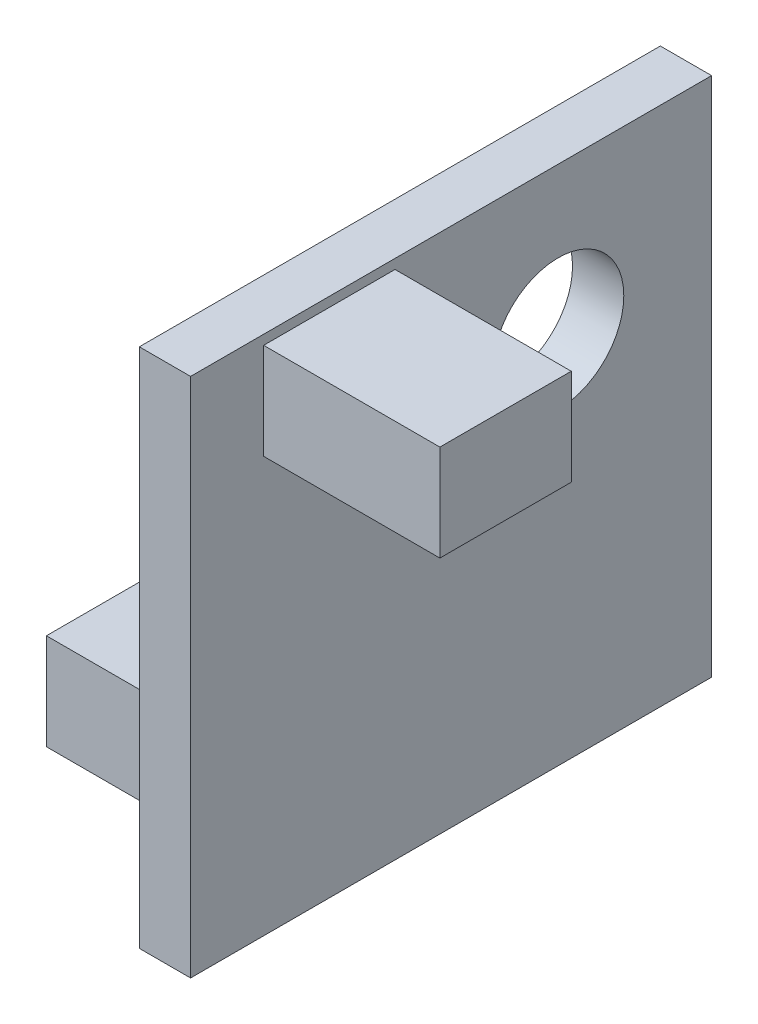
SolidWorks part; units mm, degrees
ref_plane "Front Plane" through (0, 0, 0) normal (0, 0, 1) x (1, 0, 0)
ref_plane "Top Plane" through (0, 0, 0) normal (0, 1, 0) x (1, 0, 0)
ref_plane "Right Plane" through (0, 0, 0) normal (1, 0, 0) x (0, 0, -1)
sketch "Sketch1" plane through (0, 0, 0) normal (1, 0, 0) x (0, 0, -1)
  line L1 (0, 0) -> (16.26, 0)
  line L2 (0, 0) -> (0, -16.26)
  line L3 (0, -16.26) -> (16.26, -16.26)
  line L4 (16.26, 0) -> (16.26, -16.26)
  line L5 (2.28, -0.3) -> (6.38, -0.3)
  line L6 (2.28, -0.3) -> (2.28, -3.3)
  line L7 (2.28, -3.3) -> (6.38, -3.3)
  line L8 (6.38, -0.3) -> (6.38, -3.3)
  dimension "D1" = 16.26
  dimension "D2" = 16.26
  dimension "D3" = 0.3
  dimension "D4" = 9.88
  dimension "D5" = 4.1
  dimension "D6" = 3
extrude "Boss-Extrude1" add sketch "Sketch1" along normal blind 1.6 contours L8 L5 L6 L7 | L4 L1 L2 L3 L5 L8 L7 L6 region at (0, -8.4389, -8.3154) region at (0, -1.8, -4.33)
extrude "Boss-Extrude2" add sketch "Sketch1<3>" along normal blind 7.1 contours L8 L5 L6 L7 region at (0, -1.8, -4.33)
sketch "Sketch1<3>" plane through (0, 0, 0) normal (1, 0, 0) x (0, 0, -1) same geometry as "Sketch1"
sketch "Sketch2" plane through (1.6, 0, 0) normal (1, 0, 0) x (0, 0, -1)
  line L0 (0, -16.26) -> (16.26, -16.26) construction
  line L1 (0, 0) -> (0, -16.26) construction
  circle A0 centre (11.47, -4.58) radius 2.05
  point P4 (0, 0)
  dimension "D1" = 4.1
  dimension "D2" = 11.68
  dimension "D3" = 11.47
extrude "Cut-Extrude1" cut sketch "Sketch2" against normal through all
sketch "Sketch3" plane through (1.6, 0, 0) normal (1, 0, 0) x (0, 0, -1)
  line L0 (0, -16.26) -> (16.26, -16.26) construction
  line L1 (2, -11.26) -> (9.5, -11.26)
  line L2 (2, -11.26) -> (2, -14.26)
  line L3 (2, -14.26) -> (9.5, -14.26)
  line L4 (9.5, -11.26) -> (9.5, -14.26)
  line L5 (0, 0) -> (0, -16.26) construction
  dimension "D1" = 3
  dimension "D2" = 7.5
  dimension "D3" = 2
  dimension "D4" = 2
extrude "Boss-Extrude3" add sketch "Sketch3" against normal blind 6.5
